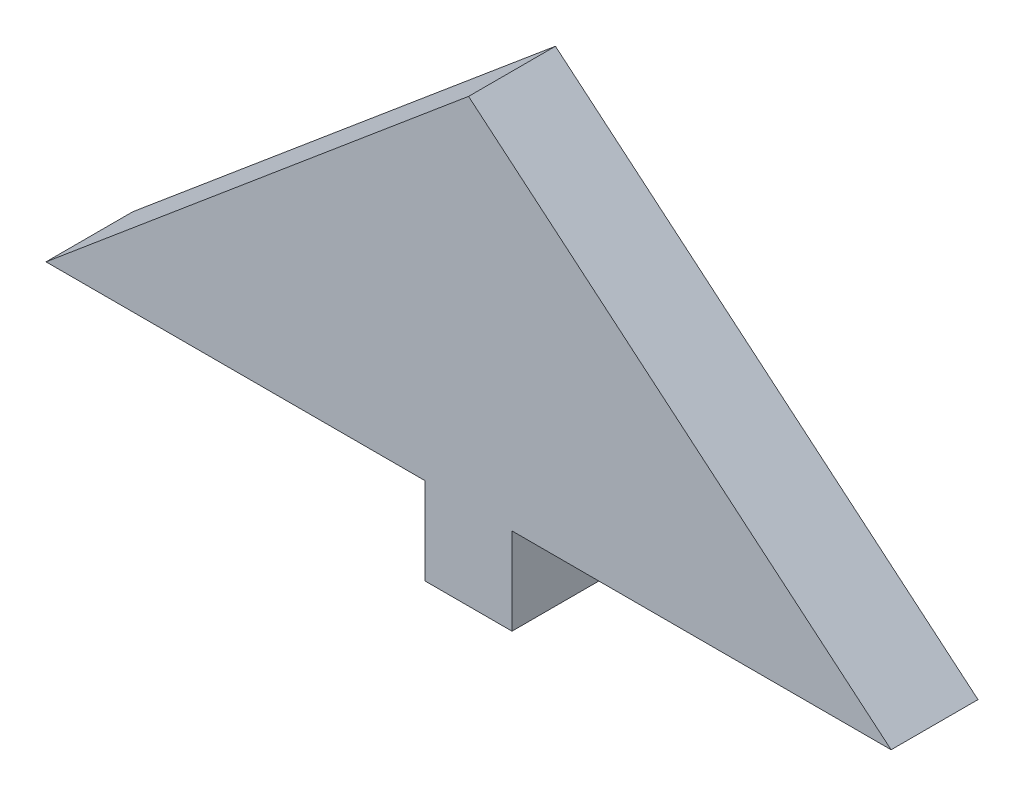
SolidWorks part; units mm, degrees
ref_plane "Front Plane" through (0, 0, 0) normal (0, 0, 1) x (1, 0, 0)
ref_plane "Top Plane" through (0, 0, 0) normal (0, 1, 0) x (1, 0, 0)
ref_plane "Right Plane" through (0, 0, 0) normal (1, 0, 0) x (0, 0, -1)
sketch "Sketch1" plane through (0, 0, 0) normal (0, 0, 1) x (1, 0, 0)
  line L0 (-14.5931, 3) -> (0, 15.2451)
  line L1 (0, 15.2451) -> (14.5931, 3)
  line L2 (14.5931, 3) -> (-14.5931, 3)
  line L4 (-1.5, 3) -> (1.5, 3)
  line L5 (-1.5, 3) -> (-1.5, 0)
  line L6 (-1.5, 0) -> (1.5, 0)
  line L7 (1.5, 3) -> (1.5, 0)
  point P7 (0, 0)
  dimension "D1" = 3
  dimension "D2" = 40
  dimension "D3" = 19.05
extrude "Boss-Extrude1" add sketch "Sketch1" along normal mid plane 3 contours L7 L2 L5 L6 | L2 L1 L0 region at (0, 7.0817, 0) region at (0, 1.5, 0)
